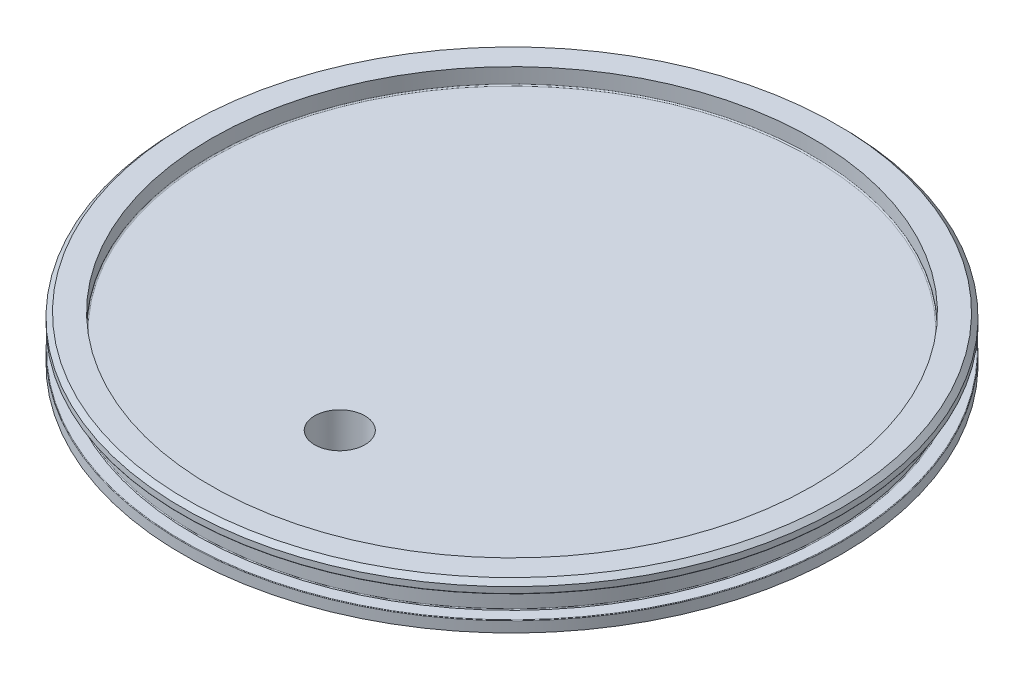
SolidWorks part; units mm, degrees
material "6061-T6 (SS)"
ref_plane "Front Plane" through (0, 0, 0) normal (0, 0, 1) x (1, 0, 0)
ref_plane "Top Plane" through (0, 0, 0) normal (0, 1, 0) x (1, 0, 0)
ref_plane "Right Plane" through (0, 0, 0) normal (1, 0, 0) x (0, 0, -1)
sketch "Sketch1" plane through (0, 0, 0) normal (0, 0, 1) x (1, 0, 0)
  line L0 (0, 48.1922) -> (0, -25.6743) construction
  line L1 (0, 0) -> (72.898, 0)
  line L2 (72.898, 0) -> (72.898, 2.4638)
  line L3 (72.898, 2.4638) -> (70.0532, 2.4638)
  line L4 (70.0532, 2.4638) -> (70.0532, 7.4422)
  line L5 (70.0532, 7.4422) -> (72.898, 7.4422)
  line L6 (72.898, 7.4422) -> (72.898, 9.906)
  line L7 (72.898, 9.906) -> (66.548, 9.906)
  line L8 (66.548, 9.906) -> (66.548, 6.35)
  line L9 (66.548, 6.35) -> (0, 6.35)
  line L10 (0, 6.35) -> (0, 0)
  dimension "D1" = 145.796
  dimension "D2" = 4.9784
  dimension "D3" = 2.8448
  dimension "D4" = 9.906
  dimension "D5" = 6.35
  dimension "D6" = 6.35
revolve "Revolve1" add sketch "Sketch1" angle 360 about L0
sketch "Sketch6" plane through (0, 0, 0) normal (0, -1, 0) x (1, 0, 0)
  circle A0 centre (0, 0) radius 66.04
  dimension "D1" = 132.08
extrude "Boss-Extrude1" add sketch "Sketch6" along normal blind 2.54
fillet "CNC ID Fillet" radius 0.1778 3 edges at (-70.0532, 7.4422, 0) (-70.0532, 2.4638, 0) (66.04, 0, 0)
fillet "CNC OD Fillet" radius 0.127 3 edges at (-72.898, 7.4422, 0) (-72.898, 2.4638, 0) (66.04, -2.54, 0)
chamfer "CNC Chamfers" distance 1.016 angle 45 1 edges at (-72.898, 9.906, 0)
fillet "CNC Bore Fillet" radius 0.254 1 edges at (-66.548, 6.35, 0)
hole_wizard "Pipe Tap Drill for 1/4 Tap - To Injector" positions "Sketch15" profile "Sketch16" hole size "1/4" standard "ANSI Inch" end condition through all
sketch "Sketch15" plane through (0, -2.54, 0) normal (0, -1, 0) x (-1, 0, 0)
  point P4 (0, -38.1)
  dimension "D1" = 38.1
sketch "Sketch16" plane through (0, -2.54, 38.1) normal (1, 0, 0) x (0, 0, -1)
  line L0 (0, 0) -> (0, 12.446)
  line L1 (0, 12.446) -> (5.5626, 12.446)
  line L2 (5.5626, 12.446) -> (5.5626, 0)
  line L5 (5.5626, 0) -> (0, 0)
  line L11 (0, -6.35) -> (0, 107.95) construction
  dimension "Thru Hole Dia." = 11.1252
  dimension "Thru Hole Depth" = 12.446
